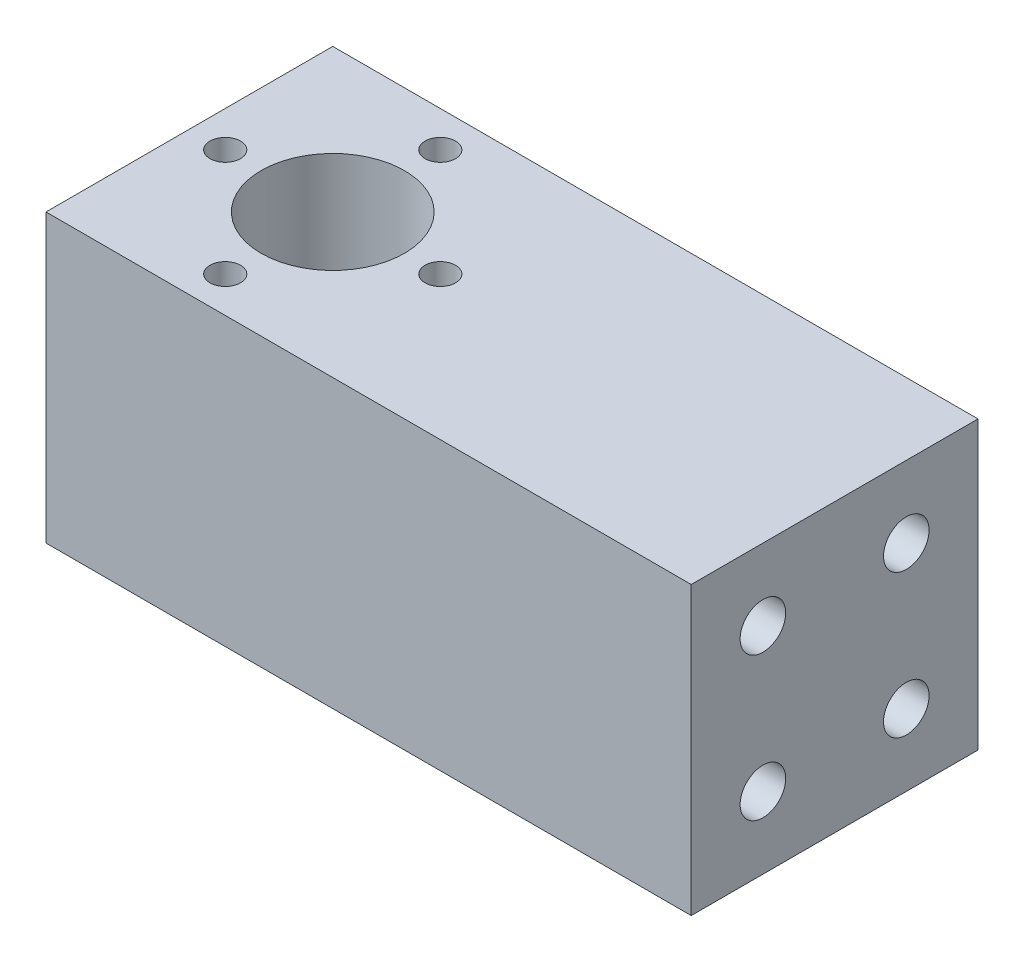
SolidWorks part; units mm, degrees
material "6061-T6 (SS)"
ref_plane "Front Plane" through (0, 0, 0) normal (0, 0, 1) x (1, 0, 0)
ref_plane "Top Plane" through (0, 0, 0) normal (0, 1, 0) x (1, 0, 0)
ref_plane "Right Plane" through (0, 0, 0) normal (1, 0, 0) x (0, 0, -1)
sketch "Sketch1" plane through (0, 0, 0) normal (0, 1, 0) x (1, 0, 0)
  line L1 (-44.45, -38.1) -> (44.45, -38.1)
  line L2 (-44.45, -38.1) -> (-44.45, 38.1)
  line L3 (-44.45, 38.1) -> (44.45, 38.1)
  line L4 (44.45, -38.1) -> (44.45, 38.1)
  line L5 (-44.45, -38.1) -> (44.45, 38.1) construction
  line L6 (-44.45, 38.1) -> (44.45, -38.1) construction
  point P0 (0, 0)
  dimension "D1" = 76.2
  dimension "D2" = 88.9
extrude "Boss-Extrude1" add sketch "Sketch1" along normal blind 12.7
sketch "Sketch2" plane through (44.45, 0, 0) normal (1, 0, 0) x (0, 0, -1)
  line L0 (-38.1, 0) -> (38.1, 0) construction
  point P0 (-6.35, 6.35)
  point P1 (6.35, 6.35)
  dimension "D1" = 6.35
  dimension "D2" = 6.35
  dimension "D3" = 6.35
sketch "Sketch9" plane through (0, 12.7, 0) normal (0, 1, 0) x (1, 0, 0)
  circle A0 centre (0, 0) radius 6.35
  dimension "D1" = 12.7
extrude "Cut-Extrude2" cut sketch "Sketch9" against normal through all
fillet "Fillet1" radius 38.1 2 edges at (-44.45, 6.35, -38.1) (-44.45, 6.35, 38.1)
sketch "Sketch10" plane through (0, 12.7, 0) normal (0, 1, 0) x (1, 0, 0)
  point P0 (-9.525, 0)
  dimension "D1" = 9.525
hole_wizard "#10-32 Tapped Hole1" positions "Sketch4" profile "Sketch5" tap size "#10-32" standard "ANSI Inch"
sketch "Sketch4" plane through (44.45, 0, 0) normal (1, 0, 0) x (0, 0, -1)
  point P0 (-6.35, 6.35)
  point P3 (6.35, 6.35)
sketch "Sketch5" plane through (44.45, 6.35, 6.35) normal (0, 1, 0) x (0, 0, -1)
  line L0 (0, 0) -> (0, 10.8653)
  line L1 (0, 10.8653) -> (2.0193, 9.652)
  line L2 (2.0193, 9.652) -> (2.0193, 0)
  line L5 (2.0193, 0) -> (0, 0)
  line L10 (0, 10.8653) -> (-2.0193, 9.652) construction
  line L11 (0, -6.35) -> (0, 107.95) construction
  dimension "Tap Drill Dia." = 4.0386
  dimension "Tap Drill Depth" = 9.652
  dimension "Drill Angle" = 118
cosmetic thread "Hole Thread1" parameters "D1"=6.35, "D2"=4.826
cosmetic thread "Hole Thread2" parameters "D1"=6.35, "D2"=4.826
sketch "Sketch13" plane through (0, 12.7, 0) normal (0, 1, 0) x (1, 0, 0)
  line L0 (44.45, 12.7) -> (-12.7, 12.7)
  line L1 (44.45, -38.1) -> (44.45, 38.1) construction
  line L2 (-12.7, -12.7) -> (44.45, -12.7)
  line L3 (-12.7, 12.7) -> (-12.7, -12.7)
  line L6 (44.45, 38.1) -> (-6.35, 38.1)
  line L7 (-6.35, -38.1) -> (44.45, -38.1)
  line L8 (44.45, -38.1) -> (44.45, 38.1)
  line L9 (44.45, 38.1) -> (-6.35, 38.1)
  line L10 (-6.35, -38.1) -> (44.45, -38.1)
  line L11 (44.45, -38.1) -> (44.45, 38.1)
  circle A0 centre (0, 0) radius 6.35 construction
  arc A3 (-6.35, 38.1) -> (-44.45, 0) centre (-6.35, 0) ccw
  arc A4 (-44.45, 0) -> (-6.35, -38.1) centre (-6.35, 0) ccw
  arc A5 (-6.35, 38.1) -> (-44.45, 0) centre (-6.35, 0) ccw
  arc A6 (-44.45, 0) -> (-6.35, -38.1) centre (-6.35, 0) ccw
  line M6 (44.45, 38.1) -> (-6.35, 38.1)
  arc M7 (-6.35, 38.1) -> (-44.45, 0) centre (-6.35, 0) ccw
  arc M8 (-44.45, 0) -> (-6.35, -38.1) centre (-6.35, 0) ccw
  line M9 (-6.35, -38.1) -> (44.45, -38.1)
  line M10 (44.45, -38.1) -> (44.45, 38.1)
  dimension "D1" = 12.7
  dimension "D2" = 0
  dimension "D3" = 25.4
  dimension "D4" = 12.7
extrude "Cut-Extrude3" cut sketch "Sketch13" against normal through all contours L3 L0 L2 M10 M6 M7 M8 M9
mirror "Mirror2" about plane through (0, 0, 0) normal (0, -1, 0) of bodies 123
hole_wizard "#6-32 Tapped Hole1" positions "Sketch12" profile "Sketch11" tap size "#6-32" standard "ANSI Inch" end condition through all
sketch "Sketch12" plane through (0, 12.7, 0) normal (0, 1, 0) x (1, 0, 0)
  point P0 (-9.525, 0)
sketch "Sketch11" plane through (-9.525, 12.7, 0) normal (1, 0, 0) x (0, 0, 1)
  line L0 (0, 0) -> (0, 25.4)
  line L1 (0, 25.4) -> (1.3525, 25.4)
  line L2 (1.3525, 25.4) -> (1.3525, 0)
  line L5 (1.3525, 0) -> (0, 0)
  line L11 (0, -6.35) -> (0, 107.95) construction
  dimension "Thru Tap Drill Dia." = 2.7051
  dimension "Thru Tap Drill Depth" = 25.4
cosmetic thread "Hole Thread3" parameters "D2"=3.5052
pattern_circular "CirPattern1" count 4 over 360 about axis through (0, 0, 0) along (0, 1, 0) of "#6-32 Tapped Hole1"
